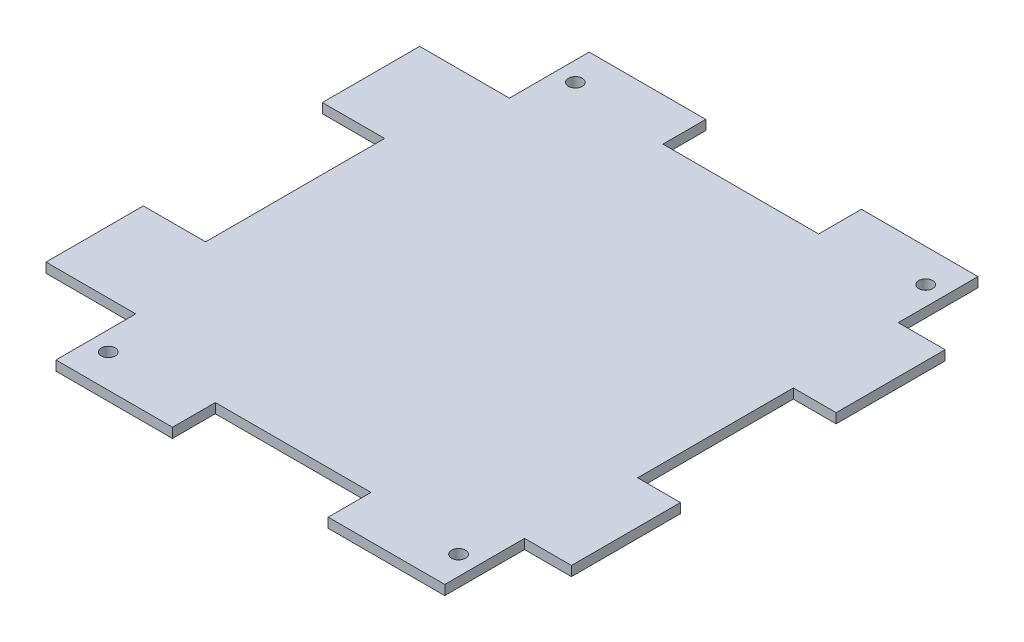
SolidWorks part; units mm, degrees
ref_plane "Front Plane" through (0, 0, 0) normal (0, 0, 1) x (1, 0, 0)
ref_plane "Top Plane" through (0, 0, 0) normal (0, 1, 0) x (1, 0, 0)
ref_plane "Right Plane" through (0, 0, 0) normal (1, 0, 0) x (0, 0, -1)
sketch "Sketch1" plane through (0, 0, 0) normal (0, 1, 0) x (1, 0, 0)
  line L0 (-25.4, 86.995) -> (-63.434, 86.995)
  line L1 (-88.9, -101.6) -> (88.9, -101.6) construction
  line L2 (101.6, -88.9) -> (101.6, 88.9) construction
  line L3 (88.9, 101.6) -> (-88.9, 101.6) construction
  line L4 (-92.7125, -60.96) -> (-63.434, -60.96)
  line L5 (-63.434, -60.96) -> (-63.434, -86.995)
  line L6 (-63.434, -86.995) -> (-25.4, -86.995)
  line L7 (63.4314, -86.995) -> (63.4314, -60.96)
  line L8 (63.4314, -60.96) -> (78.74, -60.96)
  line L9 (78.74, -60.96) -> (78.74, -25.4)
  line L10 (78.74, 60.96) -> (63.4314, 60.96)
  line L11 (63.4314, 60.96) -> (63.4314, 86.995)
  line L12 (63.4314, 86.995) -> (25.4, 86.995)
  line L13 (-63.434, 86.995) -> (-63.434, 60.96)
  line L14 (-63.434, 60.96) -> (-92.7125, 60.96)
  line L15 (-92.7125, 60.96) -> (-92.7125, 29.21)
  line L16 (-92.7125, -29.21) -> (-92.7125, -60.96)
  line L17 (-92.7125, -29.21) -> (-72.3925, -29.21)
  line L19 (-92.7125, 29.21) -> (-72.3925, 29.21)
  line L20 (-72.3925, -29.21) -> (-72.3925, 29.21)
  line L22 (-25.4, 86.995) -> (-25.4, 73.025)
  line L23 (-25.4, 73.025) -> (25.4, 73.025)
  line L24 (25.4, 86.995) -> (25.4, 73.025)
  line L25 (78.74, 25.4) -> (64.77, 25.4)
  line L27 (78.74, -25.4) -> (64.77, -25.4)
  line L28 (64.77, 25.4) -> (64.77, -25.4)
  line L30 (25.4, -86.995) -> (25.4, -73.025)
  line L31 (25.4, -73.025) -> (-25.4, -73.025)
  line L32 (-25.4, -86.995) -> (-25.4, -73.025)
  line L33 (78.74, 25.4) -> (78.74, 60.96)
  line L34 (25.4, -86.995) -> (63.4314, -86.995)
  arc A0 (88.9, -101.6) -> (101.6, -88.9) centre (88.9, -88.9) ccw construction
  arc A1 (-101.6, -88.9) -> (-88.9, -101.6) centre (-88.9, -88.9) ccw construction
  arc A2 (101.6, 88.9) -> (88.9, 101.6) centre (88.9, 88.9) ccw construction
  arc A3 (-101.6, 88.9) -> (-88.9, 101.6) centre (-88.9, 88.9) cw construction
  circle A4 centre (-57.15, 76.2) radius 2.286
  circle A5 centre (57.15, 76.2) radius 2.286
  circle A6 centre (57.15, -76.2) radius 2.286
  circle A7 centre (-57.15, -76.2) radius 2.286
  point P3 (0, 101.6)
  point P5 (101.6, 0)
  point P13 (101.6, 101.6)
  point P16 (-101.6, 101.6)
  point P38 (-72.3925, 0)
  point P55 (0, -73.025)
  point P56 (0, 73.025)
  point P57 (64.77, 0)
  dimension "D2" = 12.7
  dimension "D11" = 4.572
  dimension "D1" = 203.2
  dimension "D3" = 203.2
  dimension "D4" = 22.86
  dimension "D5" = 15.3086
  dimension "D6" = 126.8654
  dimension "D7" = 173.99
  dimension "D10" = 29.2786
  dimension "D12" = 50.8
  dimension "D13" = 25.4
  dimension "D14" = 44.45
  dimension "D15" = 25.4
  dimension "D16" = 58.42
  dimension "D17" = 20.32
  dimension "D18" = 13.97
  dimension "1" = 31.75
extrude "Boss-Extrude1" add sketch "Sketch1" along normal blind 3.175
